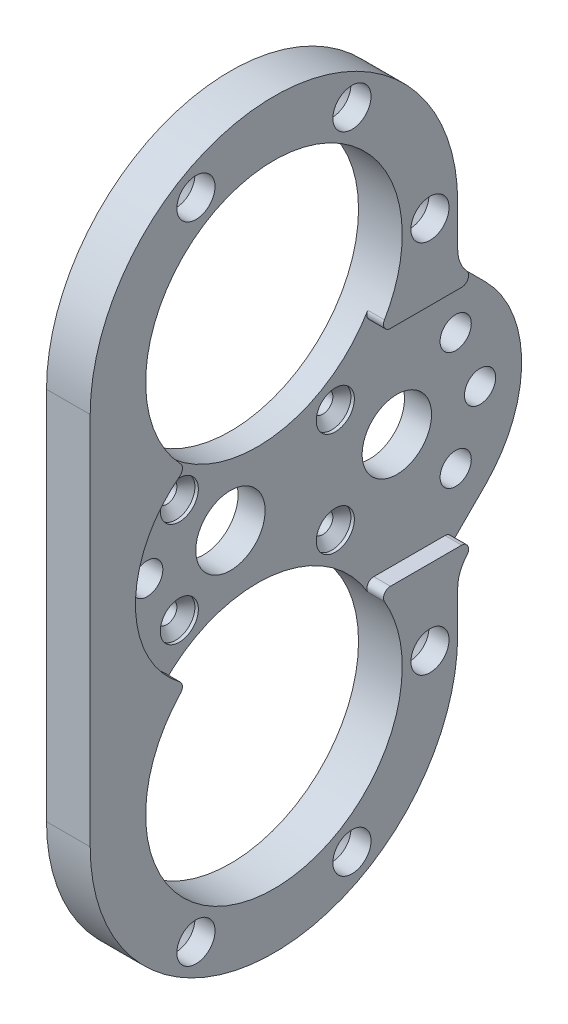
SolidWorks part; units mm, degrees
ref_plane "1" through (0, 0, 0) normal (0, 0, 1) x (1, 0, 0)
ref_plane "2" through (0, 0, 0) normal (0, 1, 0) x (1, 0, 0)
ref_plane "3" through (0, 0, 0) normal (1, 0, 0) x (0, 0, -1)
ref_plane "Front Plane" through (0, 0, 0) normal (0, -1, 0) x (1, 0, 0)
ref_plane "Right Plane" through (0, 0, 0) normal (1, 0, 0) x (0, 1, 0)
ref_plane "Top Plane" through (0, 0, 0) normal (0, 0, 1) x (1, 0, 0)
imported_body "Imported1" [suppressed]
move or copy body "Body-Move/Copy1" [suppressed] bodies to move or copy 110 copy no rotation origin (0, 0, 0) rotation axis (1, 0, 0) rotation angle 90
move or copy body "Body-Move/Copy2" [suppressed] bodies to move or copy 111 copy no translate (0, 0, 4.1741) parameters "D1"=0, "D2"=0, "D3"=4.1741
move or copy body "Body-Move/Copy3" [suppressed] bodies to move or copy 112 copy no translate (0, 0, 80) parameters "D1"=0, "D2"=0, "D3"=80
sketch "Sketch1" plane through (0, 0, 0) normal (1, 0, 0) x (0, 1, 0)
  line L0 (-27, 0) -> (0, -92.1249) construction
  line L1 (0, -92.1249) -> (27, 0) construction
  line L2 (-27, 0) -> (27, 0) construction
  line L3 (0, -92.1249) -> (0, -105.6378) construction
  line L4 (-27, -22.5) -> (-27, 0) construction
  line L11 (-8.4853, -28.6102) -> (-4.9497, -25.0747) construction
  line L12 (0, -32.1249) -> (0, -27.1249) construction
  line L13 (8.4853, -28.6102) -> (4.9497, -25.0747) construction
  line L14 (-46.4856, 11.25) -> (-27, 0) construction
  circle A0 centre (-27, 0) radius 22.5 construction
  arc A1 (-27, 0) -> (27, 0) centre (0, -92.1249) cw construction
  circle A2 centre (0, -20.1249) radius 7 construction
  circle A3 centre (0, 15.8751) radius 2 construction
  circle A7 centre (-8.4853, -28.6102) radius 2 construction
  circle A8 centre (0, -32.1249) radius 2 construction
  circle A9 centre (8.4853, -28.6102) radius 2 construction
  circle A10 centre (-46.4856, 11.25) radius 1.25 construction
  dimension "D1" = 96
  dimension "D2" = 45
  dimension "D4" = 108
  dimension "D5" = 4
  dimension "D6" = 72
  dimension "D7" = 14
  dimension "D10" = 12
  dimension "D12" = 2.5
  dimension "D3" = 54
  dimension "D8" = 45
  dimension "D9" = 45
  dimension "D11" = 120
sketch "Sketch2" plane through (0, 0, 0) normal (1, 0, 0) x (0, 1, 0)
  line L6 (-12.7279, -32.8528) -> (-17.6163, -27.9645)
  line L7 (0, 26.5) -> (0, -38.1249)
  line L8 (0, -92.1249) -> (0, -105.6378) construction
  line L9 (-27, -26.5) -> (-21.1518, -26.5)
  line L12 (-27, 26.5) -> (0, 26.5)
  circle A2 centre (0, -20.1249) radius 7 construction
  arc A3 (-27, 26.5) -> (-27, -26.5) centre (-27, 0) ccw
  arc A4 (0, -38.1249) -> (-12.7279, -32.8528) centre (0, -20.1249) cw
  circle A5 centre (-27, 0) radius 22.5 construction
  arc A6 (-21.1518, -26.5) -> (-17.6163, -27.9645) centre (-21.1518, -31.5) cw
  dimension "D2" = 18
  dimension "D3" = 53
  dimension "D4" = 5
  dimension "D1" = 45
extrude "Boss-Extrude1" add sketch "Sketch2" against normal blind 4 separate body
other "Move Face4" face at (0, -18.9107, -14.2652) offset 2.5 parameters "D1"=2.5
hole_wizard "CSK for M2.5 Flat Head Machine Screw1" positions "Sketch17" profile "Sketch18" countersink size "M2.5" standard "ANSI Metric" end condition through all
sketch "Sketch17" plane through (2.5, 0, 0) normal (1, 0, 0) x (0, 0, -1)
  circle A0 centre (-11.25, -46.4856) radius 1.25 construction
  point P0 (-11.25, -46.4856)
sketch "Sketch18" plane through (2.5, -46.4856, 11.25) normal (0, 1, 0) x (0, 0, -1)
  line L0 (0, 0) -> (0, 6.5)
  line L1 (0, 6.5) -> (1.45, 6.5)
  line L2 (1.45, 6.5) -> (1.45, 4.3)
  line L3 (1.45, 4.3) -> (2.75, 3)
  line L4 (2.75, 3) -> (2.75, 0)
  line L6 (2.75, 0) -> (0, 0)
  line L7 (-1.45, 4.3) -> (-2.75, 3) construction
  line L11 (0, -6.35) -> (0, 107.95) construction
  dimension "Thru Hole Dia." = 2.9
  dimension "Thru Hole Depth" = 6.5
  dimension "C'Sink Dia." = 5.5
  dimension "C'Sink Angle" = 90
  dimension "Head Clearance" = 3
pattern_circular "CirPattern1" count 6 over 360 about axis through (-4, -27, 0) along (1, 0, 0) skipping 5 of "CSK for M2.5 Flat Head Machine Screw1"
sketch "Sketch9" plane through (0, 0, 0) normal (1, 0, 0) x (0, 1, 0)
  line L0 (0, 3.8751) -> (0, -20.1249) construction
  circle A5 centre (0, 3.8751) radius 5
  circle A6 centre (0, -20.1249) radius 5
  arc A7 (27, 0) -> (-27, 0) centre (0, -92.1249) ccw construction
  dimension "D2" = 96
  dimension "D1" = 10
  dimension "D3" = 24
extrude "Cut-Extrude1" cut sketch "Sketch9" along normal through all both and the other way through all from surface starting at face at (-4, -7.5144, 9.8)
sketch "Sketch10" plane through (0, 0, 0) normal (1, 0, 0) x (0, 1, 0)
  line L0 (0, -92.1249) -> (0, -105.6378) construction
  line L1 (2.0785, 12.2751) -> (4.1569, 15.8751)
  line L2 (4.1569, 15.8751) -> (2.0785, 19.4751)
  line L3 (2.0785, 19.4751) -> (-2.0785, 19.4751)
  line L4 (-2.0785, 19.4751) -> (-4.1569, 15.8751)
  line L5 (-4.1569, 15.8751) -> (-2.0785, 12.2751)
  line L6 (-2.0785, 12.2751) -> (2.0785, 12.2751)
  line L7 (-5.5459, -31.5496) -> (-4.47, -27.5343)
  line L8 (-4.47, -27.5343) -> (-7.4094, -24.5949)
  line L9 (-7.4094, -24.5949) -> (-11.4247, -25.6708)
  line L10 (-11.4247, -25.6708) -> (-12.5006, -29.6861)
  line L11 (-12.5006, -29.6861) -> (-9.5612, -32.6255)
  line L12 (-9.5612, -32.6255) -> (-5.5459, -31.5496)
  line L13 (4.1569, -32.1249) -> (2.0785, -28.5249)
  line L14 (2.0785, -28.5249) -> (-2.0785, -28.5249)
  line L15 (-2.0785, -28.5249) -> (-4.1569, -32.1249)
  line L16 (-4.1569, -32.1249) -> (-2.0785, -35.7249)
  line L17 (-2.0785, -35.7249) -> (2.0785, -35.7249)
  line L18 (2.0785, -35.7249) -> (4.1569, -32.1249)
  line L19 (12.5006, -29.6861) -> (11.4247, -25.6708)
  line L20 (11.4247, -25.6708) -> (7.4094, -24.5949)
  line L21 (7.4094, -24.5949) -> (4.47, -27.5343)
  line L22 (4.47, -27.5343) -> (5.5459, -31.5496)
  line L23 (5.5459, -31.5496) -> (9.5612, -32.6255)
  line L24 (9.5612, -32.6255) -> (12.5006, -29.6861)
  line L25 (-8.4853, -28.6102) -> (-4.9497, -25.0747) construction
  line L26 (0, -32.1249) -> (0, -27.1249) construction
  line L27 (8.4853, -28.6102) -> (4.9497, -25.0747) construction
  line L29 (-51, 17.2182) -> (-47.4, 19.2966)
  line L30 (-47.4, 19.2966) -> (-47.4, 23.4535)
  line L31 (-47.4, 23.4535) -> (-51, 25.532)
  line L32 (-51, 25.532) -> (-54.6, 23.4535)
  line L33 (-54.6, 23.4535) -> (-54.6, 19.2966)
  line L34 (-54.6, 19.2966) -> (-51, 17.2182)
  circle A0 centre (0, 15.8751) radius 3.6 construction
  circle A1 centre (-8.4853, -28.6102) radius 3.6 construction
  circle A2 centre (0, -32.1249) radius 3.6 construction
  circle A3 centre (8.4853, -28.6102) radius 3.6 construction
  circle A4 centre (0, 15.8751) radius 2 construction
  circle A5 centre (-8.4853, -28.6102) radius 2 construction
  circle A6 centre (0, -32.1249) radius 2 construction
  circle A7 centre (8.4853, -28.6102) radius 2 construction
  circle A8 centre (-51, 21.3751) radius 3.6 construction
  circle A11 centre (0, -20.1249) radius 7 construction
  dimension "D1" = 7.2
  dimension "D2" = 41.5
  dimension "D3" = 51
hole_wizard "M4 Clearance Hole1" positions "Sketch19" profile "Sketch20" hole size "M4" standard "ANSI Metric" end condition through all
sketch "Sketch19" plane through (-4, 0, 0) normal (-1, 0, 0) x (0, 0, 1)
  circle A0 centre (15.8751, 0) radius 3.6 construction
  circle A1 centre (-28.6102, -8.4853) radius 3.6 construction
  circle A2 centre (-32.1249, 0) radius 3.6 construction
  point P0 (15.8751, 0)
  point P2 (-28.6102, -8.4853)
  point P4 (-32.1249, 0)
sketch "Sketch20" plane through (-4, 0, 15.8751) normal (0, 1, 0) x (0, 0, 1)
  line L0 (0, 0) -> (0, 6.5)
  line L1 (0, 6.5) -> (2.25, 6.5)
  line L2 (2.25, 6.5) -> (2.25, 0)
  line L5 (2.25, 0) -> (0, 0)
  line L11 (0, -6.35) -> (0, 107.95) construction
  dimension "Thru Hole Dia." = 4.5
  dimension "Thru Hole Depth" = 6.5
sketch "Sketch11" plane through (0, 0, 0) normal (1, 0, 0) x (0, 1, 0)
  circle A0 centre (-27, 0) radius 18.5
  circle A1 centre (-27, 0) radius 22.5 construction
  dimension "D1" = 37
extrude "Cut-Extrude3" cut sketch "Sketch11" against normal through all both and the other way through all
sketch "Sketch14" plane through (0, 0, 0) normal (1, 0, 0) x (0, 1, 0)
  line L0 (0, 3.8751) -> (0, -92.1249) construction
  line L1 (16, 3.8751) -> (16, -92.1249)
  line L2 (-16, 3.8751) -> (-16, -92.1249)
  arc A0 (16, 3.8751) -> (-16, 3.8751) centre (0, 3.8751) ccw
  arc A1 (-16, -92.1249) -> (16, -92.1249) centre (0, -92.1249) ccw
  arc A3 (27, 0) -> (-27, 0) centre (0, -92.1249) ccw construction
  point P2 (0, -44.1249)
  dimension "D1" = 16
  dimension "D2" = 96
extrude "Cut-Extrude4" cut sketch "Sketch14" along normal through all
other "Move Face3" flip direction yes face at (1.25, -16, -22.2276) face at (1.25, -7.1788, 17.0778) offset 0.1 parameters "D1"=0.1
fillet "Fillet1" radius 1 3 edges at (1.25, -16.1, -29.4808) (1.25, -16.1, -14.9479) (1.25, -13.4995, 12.6486)
sketch "Sketch12" plane through (0, 0, 0) normal (1, 0, 0) x (0, 1, 0)
  line L0 (-42.85, 25.8751) -> (-37.15, 25.8751)
  line L1 (-42.85, 25.8751) -> (-42.85, 23.4751)
  line L2 (-37.15, 25.8751) -> (-37.15, 23.4751)
  line L3 (-42.85, 23.4751) -> (-37.15, 23.4751)
  line L4 (-2.85, 25.8751) -> (2.85, 25.8751)
  line L5 (-2.85, 25.8751) -> (-2.85, 23.4751)
  line L6 (2.85, 25.8751) -> (2.85, 23.4751)
  line L7 (-2.85, 23.4751) -> (2.85, 23.4751)
  line L8 (-40, 25.8751) -> (-40, 31.3729) construction
  line L9 (0, 25.8751) -> (0, 32.0045) construction
  circle A0 centre (0, -20.1249) radius 7 construction
  dimension "D4" = 46
  dimension "D1" = 40
  dimension "D2" = 2.4
  dimension "D3" = 5.7
sketch "Sketch13" plane through (0, 0, 0) normal (0, 0, 1) x (1, 0, 0)
  line L8 (0, -2.4042) -> (0, -37.5958) construction
  line L9 (0, -2.4042) -> (2.4042, 0)
  line L10 (2.4042, 0) -> (0, 2.4042)
  line L11 (0, 2.4042) -> (-2.4042, 0)
  line L12 (-2.4042, 0) -> (0, -2.4042)
  line L13 (0, -42.4042) -> (2.4042, -40)
  line L14 (2.4042, -40) -> (0, -37.5958)
  line L15 (0, -37.5958) -> (-2.4042, -40)
  line L16 (-2.4042, -40) -> (0, -42.4042)
  line L17 (0, 2.4042) -> (0, 0) construction
  line L18 (0, -42.4042) -> (0, -40) construction
  circle A0 centre (0, 0) radius 1.7 construction
  circle A1 centre (0, -40) radius 1.7 construction
  dimension "D1" = 3.4
  dimension "D2" = 40
other "Move Face1" flip direction yes face at (-4, -27, -18.5) face at (2.5, -46.4856, 8.5) offset 0.1 parameters "D1"=0.1
mirror "Mirror1" about plane through (0, 0, 0) normal (0, -1, 0) of bodies 102
